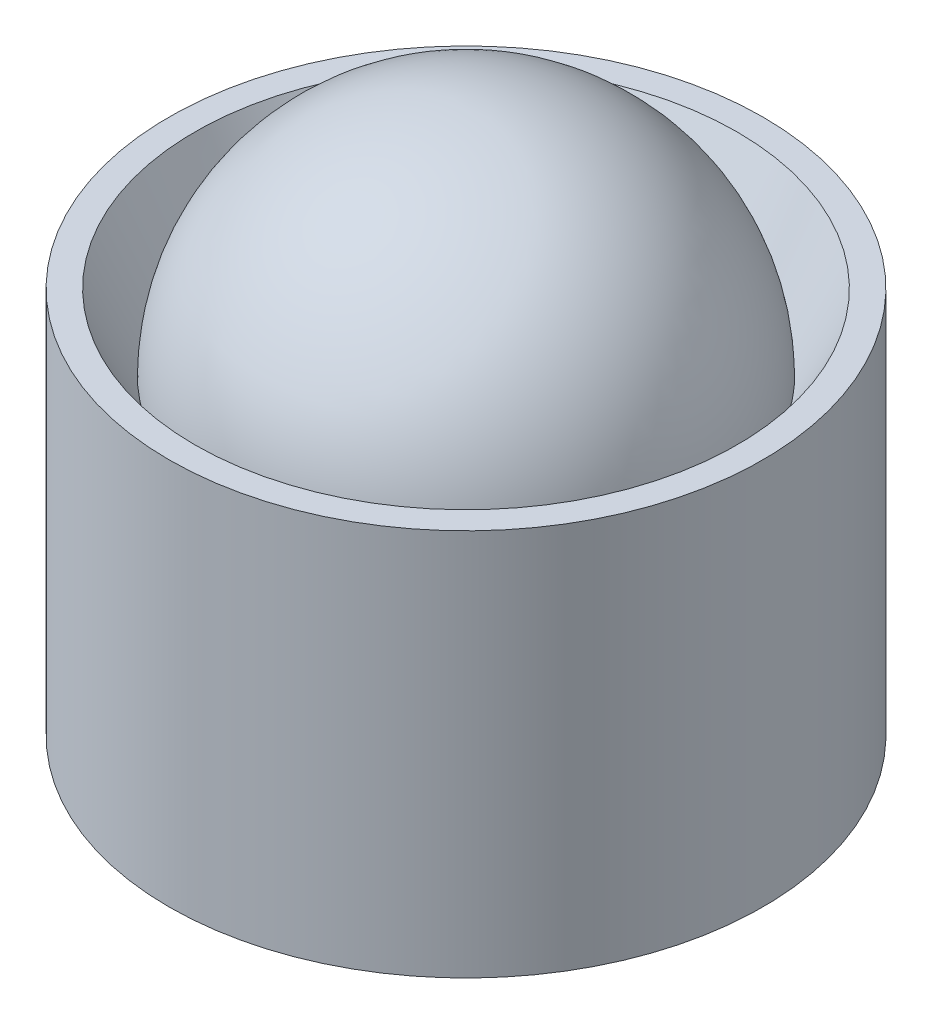
SolidWorks part; units mm, degrees
ref_plane "Front Plane" through (0, 0, 0) normal (0, 0, 1) x (1, 0, 0)
ref_plane "Top Plane" through (0, 0, 0) normal (0, 1, 0) x (1, 0, 0)
ref_plane "Right Plane" through (0, 0, 0) normal (1, 0, 0) x (0, 0, -1)
sketch "Sketch1" plane through (0, 0, 0) normal (0, 1, 0) x (1, 0, 0)
  circle A0 centre (0, 0) radius 11.5
  circle A1 centre (0, 0) radius 5.5
  circle A2 centre (7.5, 0) radius 1.25
  circle A3 centre (-7.5, 0) radius 1.25
  dimension "D1" = 23
  dimension "D2" = 11
  dimension "D3" = 2.5
  dimension "D4" = 2.5
  dimension "D5" = 7.5
  dimension "D6" = 7.5
extrude "Boss-Extrude1" add sketch "Sketch1" along normal blind 15
chamfer "Chamfer1" distance 5 distance2 10 1 edges at (0, 15, 5.5) first distance on face at (7.5, 15, 1.25)
ref_plane "Plane1" through (0, 21, 0) normal (0, -1, 0) x (-1, 0, 0)
ref_plane "Plane2" through (0, 12, 0) normal (0, -1, 0) x (-1, 0, 0)
sketch "Sketch2" plane through (0, 12, 0) normal (0, -1, 0) x (-1, 0, 0)
  circle A0 centre (0, 0) radius 9
  dimension "D1" = 18
extrude "Boss-Extrude2" add sketch "Sketch2" along normal mid plane 18 separate body
fillet "Fillet1" radius 9 2 edges at (0, 21, -9) (0, 3, -9)
